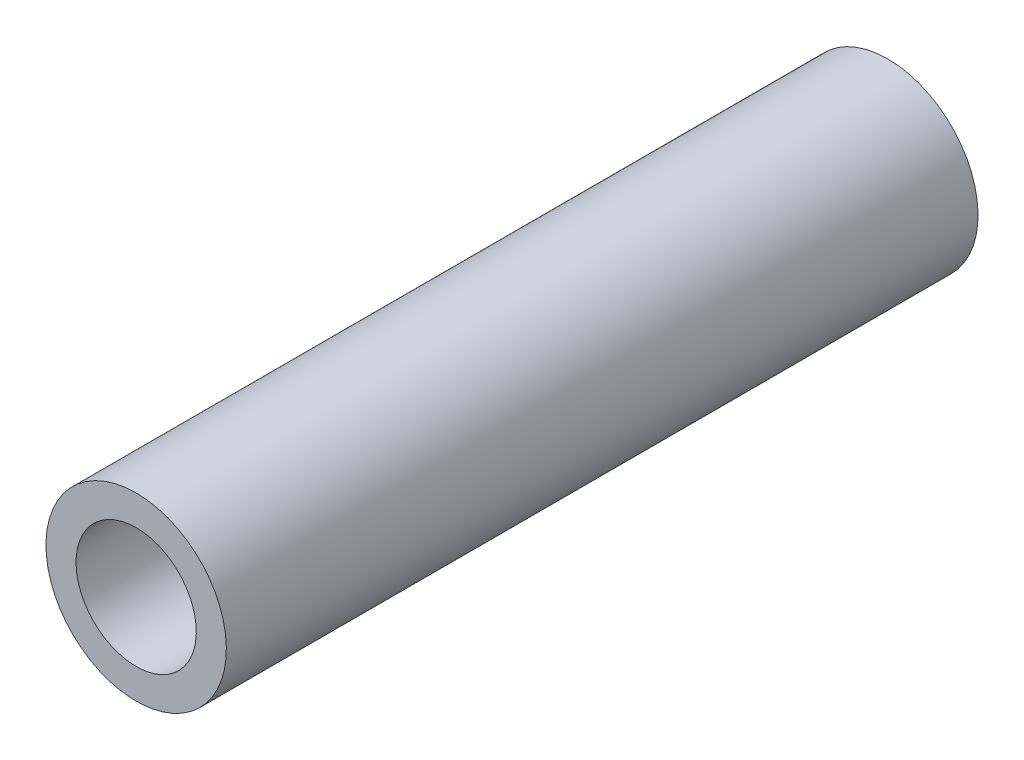
SolidWorks part; units mm, degrees
material "Plain Carbon Steel"
ref_plane "Front Plane" through (0, 0, 0) normal (0, 0, 1) x (1, 0, 0)
ref_plane "Top Plane" through (0, 0, 0) normal (0, 1, 0) x (1, 0, 0)
ref_plane "Right Plane" through (0, 0, 0) normal (1, 0, 0) x (0, 0, -1)
sketch "Sketch1" plane through (0, 0, 0) normal (1, 0, 0) x (0, 0, -1)
  line L0 (10, 0) -> (10, 4)
  line L1 (10, 4) -> (0, 4)
  line L2 (0, 4) -> (0, 6)
  line L3 (0, 6) -> (50, 6)
  line L4 (50, 6) -> (50, 4)
  line L5 (50, 4) -> (40, 4)
  line L6 (40, 4) -> (40, 0)
  line L7 (40, 0) -> (10, 0)
  dimension "D1" = 50
  dimension "D2" = 6
  dimension "D3" = 4
  dimension "D4" = 10
revolve "Revolve1" add sketch "Sketch1" angle 360 about L7
